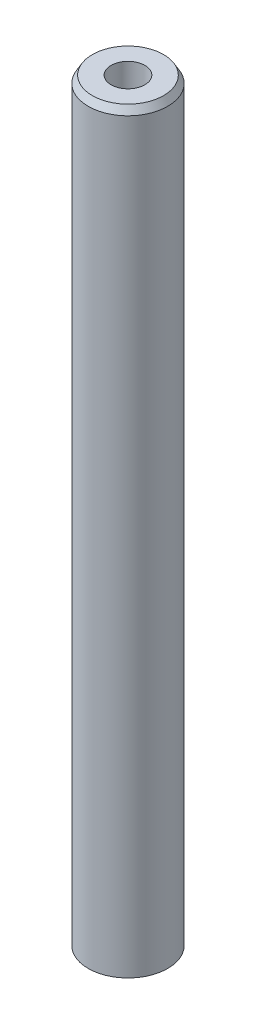
SolidWorks part; units mm, degrees
ref_plane "Front Plane" through (0, 0, 0) normal (0, 0, 1) x (1, 0, 0)
ref_plane "Top Plane" through (0, 0, 0) normal (0, 1, 0) x (1, 0, 0)
ref_plane "Right Plane" through (0, 0, 0) normal (1, 0, 0) x (0, 0, -1)
sketch "Sketch1" plane through (0, 0, 0) normal (0, 1, 0) x (1, 0, 0)
  circle A0 centre (0, 0) radius 30
  dimension "SHAFT_OD" = 60
extrude "Boss-Extrude1" add sketch "Sketch1" along normal blind 571.9572
sketch "Sketch2" plane through (0, 0, 0) normal (0, 1, 0) x (1, 0, 0)
  circle A0 centre (0, 0) radius 12.7333
  dimension "BORE_D" = 25.4666
extrude "Cut-Extrude1" cut sketch "Sketch2" along normal through all
chamfer "Chamfer1" distance 5.4171 angle 30 2 edges at (0, 571.9572, 30) (0, 0, 30) first distance on face at (0, 571.9572, 30) first distance on face at (0, 0, 12.7333)
